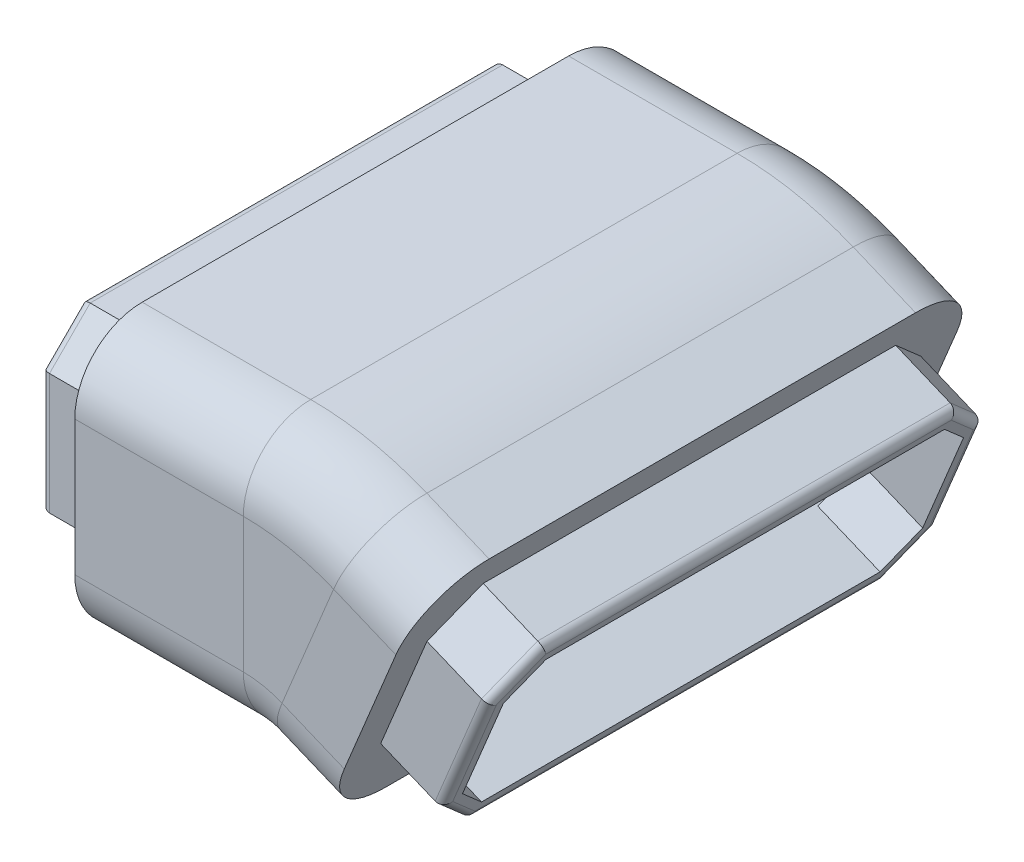
SolidWorks part; units mm, degrees
ref_plane "Front" through (0, 0, 0) normal (0, 0, 1) x (1, 0, 0)
ref_plane "Top" through (0, 0, 0) normal (0, 1, 0) x (1, 0, 0)
ref_plane "Right" through (0, 0, 0) normal (1, 0, 0) x (0, 0, -1)
sketch "Sketch2path" plane through (0, 0, 0) normal (0, 0, 1) x (1, 0, 0)
  line L0 (13.8268, -0.7612) -> (17.5224, -2.2919)
  line L1 (0, 0) -> (10, 0)
  arc A1 (10, 0) -> (13.8268, -0.7612) centre (10, -10) cw
  point P5 (11.9891, 0)
  dimension "D1" = 10
  dimension "D2" = 22.5
  dimension "D4" = 10
  dimension "D3" = 4
sketch "Sketch3" plane through (0, 0, 0) normal (1, 0, 0) x (0, 0, -1)
  line L0 (-16.65, -4) -> (-16.65, 4)
  line L1 (-12.65, 8) -> (12.65, 8)
  line L2 (16.65, 4) -> (16.65, -4)
  line L3 (12.65, -8) -> (-12.65, -8)
  line L4 (-15.65, -4) -> (-15.65, 4)
  line L5 (12.65, -7) -> (-12.65, -7)
  line L6 (0, 91.8161) -> (0, -91.8161) construction
  line L12 (15.65, 4) -> (15.65, -4)
  line L13 (-12.65, 7) -> (12.65, 7)
  arc A0 (-12.65, 8) -> (-16.65, 4) centre (-12.65, 4) ccw
  arc A1 (16.65, 4) -> (12.65, 8) centre (12.65, 4) ccw
  arc A2 (12.65, -8) -> (16.65, -4) centre (12.65, -4) ccw
  arc A3 (-16.65, -4) -> (-12.65, -8) centre (-12.65, -4) ccw
  arc A4 (-12.65, 7) -> (-15.65, 4) centre (-12.65, 4) ccw
  arc A5 (12.65, 7) -> (15.65, 4) centre (12.65, 4) cw
  arc A6 (15.65, -4) -> (12.65, -7) centre (12.65, -4) cw
  arc A7 (-15.65, -4) -> (-12.65, -7) centre (-12.65, -4) ccw
  dimension "D1" = 4
sweep "Sweep1" add profiles "Sketch3" path "Sketch2path"
ref_point "Point1S1"
ref_point "Point2S3"
ref_axis "os podluzna S1" through (0, 0, 0) along (-1, 0, 0)
ref_axis "os podluzna S3" through (17.5224, -2.2919, 0) along (0.9239, -0.3827, 0)
ref_plane "Plane4 polowki" through (0, 0, 0) normal (0, 0, 1) x (1, 0, 0)
sketch "Sketch4" plane through (0, 0, 0) normal (-1, 0, 0) x (0, 0, 1)
  line L0 (15.65, 4) -> (15.65, -4) construction
  line L1 (-12.65, 7) -> (12.65, 7) construction
  line L2 (-15.65, -4) -> (-15.65, 4) construction
  line L3 (12.65, -7) -> (-12.65, -7) construction
  line L4 (15.65, 4) -> (15.65, -4)
  line L5 (-12.65, 7) -> (12.65, 7)
  line L6 (-15.65, -4) -> (-15.65, 4)
  line L7 (12.65, -7) -> (-12.65, -7)
  line L12 (-13.65, -4) -> (-13.65, 4)
  line L13 (12.65, -5) -> (-12.65, -5)
  line L14 (13.65, 4) -> (13.65, -4)
  line L15 (-12.65, 5) -> (12.65, 5)
  arc A0 (-12.65, 5) -> (-13.65, 4) centre (-12.65, 4) ccw
  arc A1 (-13.65, -4) -> (-12.65, -5) centre (-12.65, -4) ccw
  arc A2 (12.65, -5) -> (13.65, -4) centre (12.65, -4) ccw
  arc A3 (13.65, 4) -> (12.65, 5) centre (12.65, 4) ccw
  arc A4 (15.65, 4) -> (12.65, 7) centre (12.65, 4) ccw
  arc A5 (-12.65, 7) -> (-15.65, 4) centre (-12.65, 4) ccw
  arc A6 (-15.65, -4) -> (-12.65, -7) centre (-12.65, -4) ccw
  arc A7 (12.65, -7) -> (15.65, -4) centre (12.65, -4) ccw
  dimension "D2" = 2
extrude "Boss-Extrude1" add sketch "Sketch4" along normal mid plane 8
sketch "Sketch5" plane through (-4, 0, 0) normal (-1, 0, 0) x (0, 0, 1)
  line L1 (12.65, 5) -> (-12.65, 5) construction
  line L2 (13.65, -4) -> (13.65, 4) construction
  line L3 (-12.65, -5) -> (12.65, -5) construction
  line L4 (-13.65, 4) -> (-13.65, -4) construction
  line L5 (12.65, 5) -> (-12.65, 5)
  line L6 (13.65, -4) -> (13.65, 4)
  line L7 (-12.65, -5) -> (12.65, -5)
  line L8 (-13.65, 4) -> (-13.65, -4)
  line L9 (12.65, 6) -> (-12.65, 6)
  line L10 (-14.65, 4) -> (-14.65, -4)
  line L11 (-12.65, -6) -> (12.65, -6)
  line L12 (14.65, -4) -> (14.65, 4)
  arc A0 (13.65, 4) -> (12.65, 5) centre (12.65, 4) ccw construction
  arc A1 (12.65, -5) -> (13.65, -4) centre (12.65, -4) ccw construction
  arc A2 (-13.65, -4) -> (-12.65, -5) centre (-12.65, -4) ccw construction
  arc A3 (-12.65, 5) -> (-13.65, 4) centre (-12.65, 4) ccw construction
  arc A4 (13.65, 4) -> (12.65, 5) centre (12.65, 4) ccw
  arc A5 (12.65, -5) -> (13.65, -4) centre (12.65, -4) ccw
  arc A6 (-13.65, -4) -> (-12.65, -5) centre (-12.65, -4) ccw
  arc A7 (-12.65, 5) -> (-13.65, 4) centre (-12.65, 4) ccw
  arc A8 (-12.65, 6) -> (-14.65, 4) centre (-12.65, 4) ccw
  arc A9 (-14.65, -4) -> (-12.65, -6) centre (-12.65, -4) ccw
  arc A10 (12.65, -6) -> (14.65, -4) centre (12.65, -4) ccw
  arc A11 (14.65, 4) -> (12.65, 6) centre (12.65, 4) ccw
  dimension "D1" = 1
extrude "Cut-Extrude1" cut sketch "Sketch5" against normal up to surface (4 mm away) flip side to cut up to face at (0, 0, 0)
sketch "Sketch11" plane through (-4, 0, 0) normal (-1, 0, 0) x (0, 0, 1)
  line L1 (-14.65, 6) -> (-14.65, 3.5858)
  line L2 (-12.2358, 6) -> (-14.65, 6)
  line L4 (-14.65, 3.5858) -> (-12.2358, 6)
extrude "Cut-Extrude3" cut sketch "Sketch11" against normal blind 4
sketch "Sketch12" plane through (-4, 0, 0) normal (-1, 0, 0) x (0, 0, 1)
  line L5 (-14.65, 3.5858) -> (-12.2358, 6) construction
  line L6 (-14.65, 3.5858) -> (-12.2358, 6)
  line L7 (-13.9429, 2.8787) -> (-11.5287, 5.2929)
  line L8 (-14.65, 3.5858) -> (-13.9429, 2.8787)
  line L10 (-12.2358, 6) -> (-11.5287, 5.2929)
  dimension "D2" = 1
extrude "Boss-Extrude3" add sketch "Sketch12" against normal blind 8
mirror "Mirror1" about plane through (0, 0, 0) normal (0, 0, 1) of "Cut-Extrude3", "Boss-Extrude3"
mirror "Mirror2" about plane through (0, 0, 0) normal (0, 1, 0) of "Mirror1"
fillet "Fillet3" radius 0.5 24 edges at (4, 7, 0) (4, 6.1213, -14.7713) (4, 0, -15.65) (4, -6.1213, -14.7713) (4, -7, 0) (4, -6.1213, 14.7713) (4, 0, 15.65) (4, 6.1213, 14.7713) (4, 4.0858, -12.7358) (4, 5, 0) (4, 4.0858, 12.7358) (4, 0, 13.65) (4, -4.0858, 12.7358) (4, -5, 0) (4, -4.0858, -12.7358) (4, 0, -13.65) (-4, 4.7929, 13.4429) (-4, 0, 14.65) (-4, -4.7929, 13.4429) (-4, -6, 0) (-4, -4.7929, -13.4429) (-4, 0, -14.65) (-4, 6, 0) (-4, 4.7929, -13.4429)
sketch "Sketch14" plane through (15.7666, -6.5307, 0) normal (0.9239, -0.3827, 0) x (0, 0, -1)
  line L0 (12.65, 11.588) -> (-12.65, 11.588) construction
  line L1 (15.65, 0.588) -> (15.65, 8.588) construction
  line L2 (-12.65, -2.412) -> (12.65, -2.412) construction
  line L3 (-15.65, 8.588) -> (-15.65, 0.588) construction
  line L4 (12.65, 11.588) -> (-12.65, 11.588)
  line L5 (15.65, 0.588) -> (15.65, 8.588)
  line L6 (-12.65, -2.412) -> (12.65, -2.412)
  line L7 (-15.65, 8.588) -> (-15.65, 0.588)
  line L8 (12.65, 9.588) -> (-12.65, 9.588)
  line L9 (-13.65, 8.588) -> (-13.65, 0.588)
  line L10 (-12.65, -0.412) -> (12.65, -0.412)
  line L11 (13.65, 0.588) -> (13.65, 8.588)
  arc A0 (-12.65, 11.588) -> (-15.65, 8.588) centre (-12.65, 8.588) ccw construction
  arc A1 (15.65, 8.588) -> (12.65, 11.588) centre (12.65, 8.588) ccw construction
  arc A2 (12.65, -2.412) -> (15.65, 0.588) centre (12.65, 0.588) ccw construction
  arc A3 (-15.65, 0.588) -> (-12.65, -2.412) centre (-12.65, 0.588) ccw construction
  arc A4 (-12.65, 11.588) -> (-15.65, 8.588) centre (-12.65, 8.588) ccw
  arc A5 (15.65, 8.588) -> (12.65, 11.588) centre (12.65, 8.588) ccw
  arc A6 (12.65, -2.412) -> (15.65, 0.588) centre (12.65, 0.588) ccw
  arc A7 (-15.65, 0.588) -> (-12.65, -2.412) centre (-12.65, 0.588) ccw
  arc A8 (-12.65, 9.588) -> (-13.65, 8.588) centre (-12.65, 8.588) ccw
  arc A9 (-13.65, 0.588) -> (-12.65, -0.412) centre (-12.65, 0.588) ccw
  arc A10 (12.65, -0.412) -> (13.65, 0.588) centre (12.65, 0.588) ccw
  arc A11 (13.65, 8.588) -> (12.65, 9.588) centre (12.65, 8.588) ccw
  dimension "D1" = 2
extrude "Boss-Extrude4" add sketch "Sketch14" along normal mid plane 8
sketch "Sketch15" plane through (19.4621, -8.0615, 0) normal (0.9239, -0.3827, 0) x (0, 0, -1)
  line L8 (12.65, 10.588) -> (-12.65, 10.588)
  line L9 (-14.65, 8.588) -> (-14.65, 0.588)
  line L10 (-12.65, -1.412) -> (12.65, -1.412)
  line L11 (14.65, 0.588) -> (14.65, 8.588)
  line L12 (12.65, 11.588) -> (-12.65, 11.588) construction
  line L13 (15.65, 0.588) -> (15.65, 8.588) construction
  line L14 (-12.65, -2.412) -> (12.65, -2.412) construction
  line L15 (-15.65, 8.588) -> (-15.65, 0.588) construction
  line L16 (12.65, 11.588) -> (-12.65, 11.588)
  line L17 (15.65, 0.588) -> (15.65, 8.588)
  line L18 (-12.65, -2.412) -> (12.65, -2.412)
  line L19 (-15.65, 8.588) -> (-15.65, 0.588)
  arc A8 (-12.65, 10.588) -> (-14.65, 8.588) centre (-12.65, 8.588) ccw
  arc A9 (-14.65, 0.588) -> (-12.65, -1.412) centre (-12.65, 0.588) ccw
  arc A10 (12.65, -1.412) -> (14.65, 0.588) centre (12.65, 0.588) ccw
  arc A11 (14.65, 8.588) -> (12.65, 10.588) centre (12.65, 8.588) ccw
  arc A12 (-12.65, 11.588) -> (-15.65, 8.588) centre (-12.65, 8.588) ccw construction
  arc A13 (15.65, 8.588) -> (12.65, 11.588) centre (12.65, 8.588) ccw construction
  arc A14 (12.65, -2.412) -> (15.65, 0.588) centre (12.65, 0.588) ccw construction
  arc A15 (-15.65, 0.588) -> (-12.65, -2.412) centre (-12.65, 0.588) ccw construction
  arc A16 (-12.65, 11.588) -> (-15.65, 8.588) centre (-12.65, 8.588) ccw
  arc A17 (15.65, 8.588) -> (12.65, 11.588) centre (12.65, 8.588) ccw
  arc A18 (12.65, -2.412) -> (15.65, 0.588) centre (12.65, 0.588) ccw
  arc A19 (-15.65, 0.588) -> (-12.65, -2.412) centre (-12.65, 0.588) ccw
extrude "Cut-Extrude4" cut sketch "Sketch15" against normal blind 4
sketch "Sketch16" plane through (19.4621, -8.0615, 0) normal (0.9239, -0.3827, 0) x (0, 0, -1)
  line L1 (-14.65, 8.1738) -> (-12.2358, 10.588)
  line L2 (-14.65, 8.1738) -> (-14.65, 10.588)
  line L6 (-12.2358, 10.588) -> (-14.65, 10.588)
extrude "Cut-Extrude5" cut sketch "Sketch16" against normal blind 4
sketch "Sketch17" plane through (19.4621, -8.0615, 0) normal (0.9239, -0.3827, 0) x (0, 0, -1)
  line L0 (-14.65, 8.1738) -> (-12.2358, 10.588) construction
  line L1 (-14.65, 8.1738) -> (-12.2358, 10.588)
  line L2 (-13.9429, 7.4667) -> (-11.5287, 9.8809)
  line L3 (-13.9429, 7.4667) -> (-14.65, 8.1738)
  line L4 (-12.2358, 10.588) -> (-11.5287, 9.8809)
  dimension "D1" = 1
extrude "Boss-Extrude5" add sketch "Sketch17" against normal blind 4
mirror "Mirror3" about plane through (0, 0, 0) normal (0, 0, 1) of "Cut-Extrude5", "Boss-Extrude5"
ref_plane "Plane1" through (1.7558, 4.2388, 0) normal (0.3827, 0.9239, 0) x (0.9239, -0.3827, 0)
mirror "Mirror4" about plane through (1.7558, 4.2388, 0) normal (0.3827, 0.9239, 0) of "Mirror3"
fillet "Fillet4" radius 0.5 24 edges at (13.8268, -0.7612, -13.65) (12.0255, -5.11, -13.3571) (11.9134, -5.3806, 0) (12.0255, -5.11, 13.3571) (13.8268, -0.7612, 13.65) (15.6282, 3.5876, 13.3571) (15.7403, 3.8582, 0) (15.6282, 3.5876, -13.3571) (13.8268, -0.7612, 15.65) (11.4843, -6.4166, 14.7713) (11.1481, -7.2284, 0) (11.4843, -6.4166, -14.7713) (13.8268, -0.7612, -15.65) (16.1694, 4.8942, -14.7713) (16.5056, 5.706, 0) (16.1694, 4.8942, 14.7713) (19.3837, -8.2507, -13.4429) (23.052, 0.6054, -13.4429) (21.2179, -3.8227, -14.65) (18.9218, -9.3659, 0) (19.3837, -8.2507, 13.4429) (21.2179, -3.8227, 14.65) (23.514, 1.7206, 0) (23.052, 0.6054, 13.4429)
